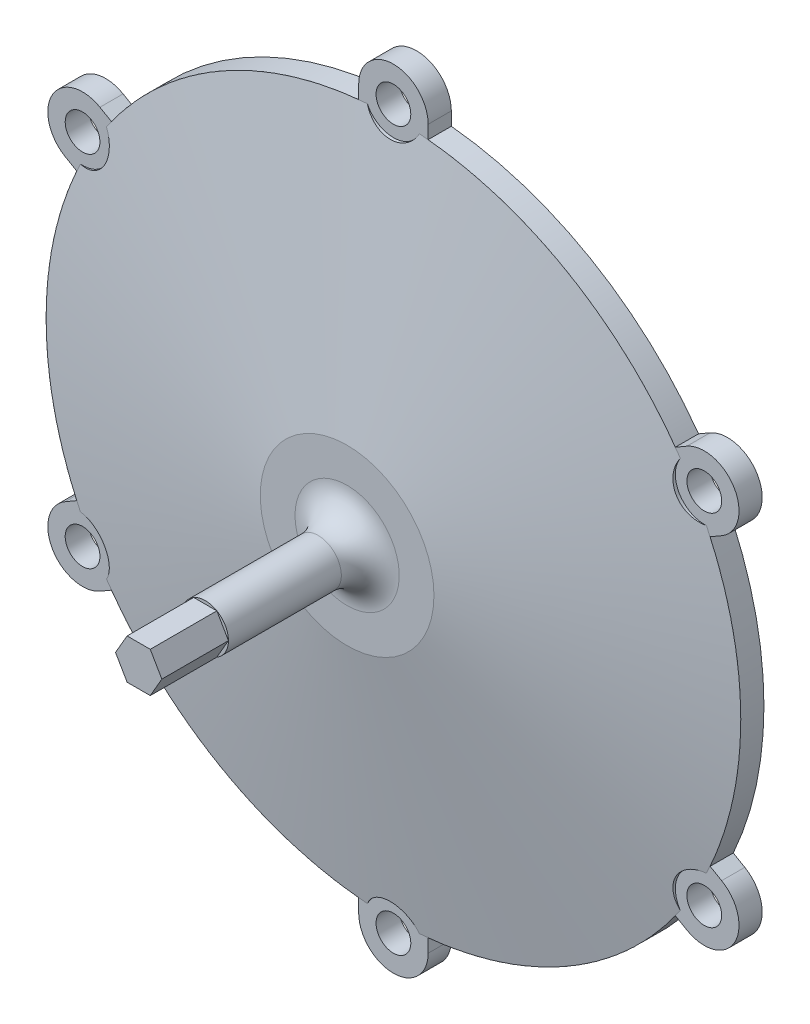
SolidWorks part; units mm, degrees
other "Markup1"
sketch "Sketch15" plane through (-60, 68, 48) normal (-0.9801, 0.1341, 0.1467) x (0.1373, -0.0767, 0.9876)
ref_plane "Front Plane" through (0, 0, 0) normal (0, 0, 1) x (1, 0, 0)
ref_plane "Top Plane" through (0, 0, 0) normal (0, 1, 0) x (1, 0, 0)
ref_plane "Right Plane" through (0, 0, 0) normal (1, 0, 0) x (0, 0, -1)
sketch "Sketch1" plane through (0, 0, 0) normal (0, 0, 1) x (1, 0, 0)
  line L0 (-6, 62) -> (-6, 59.6992)
  line L1 (6, 62) -> (6, 59.6992)
  line L2 (50.6936, 36.1962) -> (48.7011, 35.0458)
  line L3 (56.6936, 25.8038) -> (54.7011, 24.6535)
  line L4 (56.6936, -25.8038) -> (54.7011, -24.6535)
  line L5 (50.6936, -36.1962) -> (48.7011, -35.0458)
  line L6 (6, -62) -> (6, -59.6992)
  line L7 (-6, -62) -> (-6, -59.6992)
  line L8 (-50.6936, -36.1962) -> (-48.7011, -35.0458)
  line L9 (-56.6936, -25.8038) -> (-54.7011, -24.6535)
  line L10 (-56.6936, 25.8038) -> (-54.7011, 24.6535)
  line L11 (-50.6936, 36.1962) -> (-48.7011, 35.0458)
  line L12 (0, 0) -> (6, 59.6992) construction
  circle A0 centre (0, 0) radius 57
  circle A1 centre (0, 0) radius 60
  arc A2 (6, 62) -> (-6, 62) centre (0, 62) ccw
  arc A3 (56.6936, 25.8038) -> (50.6936, 36.1962) centre (53.6936, 31) ccw
  arc A4 (50.6936, -36.1962) -> (56.6936, -25.8038) centre (53.6936, -31) ccw
  arc A5 (-6, -62) -> (6, -62) centre (0, -62) ccw
  arc A6 (-56.6936, -25.8038) -> (-50.6936, -36.1962) centre (-53.6936, -31) ccw
  arc A7 (-50.6936, 36.1962) -> (-56.6936, 25.8038) centre (-53.6936, 31) ccw
  dimension "D1" = 120
  dimension "D2" = 3
  dimension "D3" = 6
  dimension "D4" = 62
  dimension "D5" = 6
extrude "Boss-Extrude1" add sketch "Sketch1" along normal blind 4 contours L11 A7 L10 A1 | L1 A2 L0 A1 | L3 A3 L2 A1 | L5 A4 L4 A1 | L7 A5 L6 A1 | L9 A6 L8 A1 | A0 A1 region at (0, 63.4372, 0) region at (0, 58.3029, 0) region at (-54.9382, 31.7186, 0) region at (54.9382, 31.7186, 0) region at (-54.9382, -31.7186, 0) region at (54.9382, -31.7186, 0) region at (0, -63.4372, 0)
sketch "Sketch3" plane through (0, 0, 0) normal (0, 1, 0) x (1, 0, 0)
  line L0 (0, -4) -> (60, -4)
  line L1 (-6, -4) -> (6, -4) construction
  line L2 (60, -4) -> (15, -12)
  line L3 (15, -12) -> (0, -12)
  line L4 (0, -12) -> (0, -4)
  line L5 (48.7011, 0) -> (6, 0) construction
  line L6 (48.7011, 0) -> (6, 0) construction
  line L7 (0, -4) -> (60, -4)
  line L8 (0, -4) -> (0, -0.5)
  line L9 (0, -0.5) -> (57, -0.5)
  line L13 (57, -0.5) -> (57, -4)
  line L15 (-57, -4) -> (57, -4) construction
  dimension "D1" = 12
  dimension "D2" = 15
  dimension "D3" = 0.5
  dimension "D4" = 3
revolve "Revolve1" add sketch "Sketch3" angle 360 about L4 region at (28.5, 0, 2.25) region at (21, 0, 7.2)
sketch "Sketch4" plane through (0, 0, 0.5) normal (0, 0, 1) x (1, 0, 0)
  circle A0 centre (0, 0) radius 14
  dimension "D1" = 28
extrude "Cut-Extrude1" cut sketch "Sketch4" along normal blind 7 contours A0
sketch "Sketch9" plane through (0, 0, 7.5) normal (0, 0, -1) x (-1, 0, 0)
  circle A0 centre (0, 0) radius 11.5
  dimension "D1" = 23
extrude "Cut-Extrude4" cut sketch "Sketch9" against normal blind 0.5
sketch "Sketch10" plane through (0, 0, 12) normal (0, 0, 1) x (1, 0, 0)
  circle A0 centre (0, 0) radius 4
  dimension "D1" = 8
extrude "Boss-Extrude2" add sketch "Sketch10" along normal blind 36
fillet "Fillet1" radius 5 1 edges at (4, 0, 12)
sketch "Sketch7" plane through (0, 0, 4) normal (0, 0, 1) x (1, 0, 0)
  circle A0 centre (0, 62) radius 3
  arc A1 (6, 62) -> (-6, 62) centre (0, 62) ccw construction
  dimension "D1" = 6
extrude "Cut-Extrude2" cut sketch "Sketch7" against normal through all
sketch "Sketch8" plane through (0, 0, 4) normal (0, 0, 1) x (1, 0, 0)
  circle A0 centre (0, 62) radius 5
  dimension "D1" = 10
extrude "Cut-Extrude3" cut sketch "Sketch8" along normal through all
pattern_circular "CirPattern6" count 6 over 360 about axis through (0, 0, 4) along (0, 0, 1) of "Cut-Extrude2", "Cut-Extrude3"
sketch "Sketch11" plane through (0, 0, 48) normal (0, 0, 1) x (1, 0, 0)
  line L5 (2, 3.4641) -> (-2, 3.4641)
  line L6 (-2, 3.4641) -> (-4, 0)
  line L7 (-4, 0) -> (-2, -3.4641)
  line L8 (-2, -3.4641) -> (2, -3.4641)
  line L9 (2, -3.4641) -> (4, 0)
  line L10 (4, 0) -> (2, 3.4641)
  circle A1 centre (0, 0) radius 3.4641 construction
  circle A2 centre (0, 0) radius 4 construction
  circle A3 centre (0, 0) radius 4
  circle M5 centre (0, 0) radius 4
extrude "Cut-Extrude5" cut sketch "Sketch11" against normal blind 11.5 contours L6 M5 | L5 M5 | L10 M5 | L9 M5 | L8 M5 | L7 M5 region at (3.1867, 1.8399, 48) region at (0, 3.6797, 48) region at (-3.1867, 1.8399, 48) region at (3.1867, -1.8399, 48) region at (-3.1867, -1.8399, 48) region at (0, -3.6797, 48)
